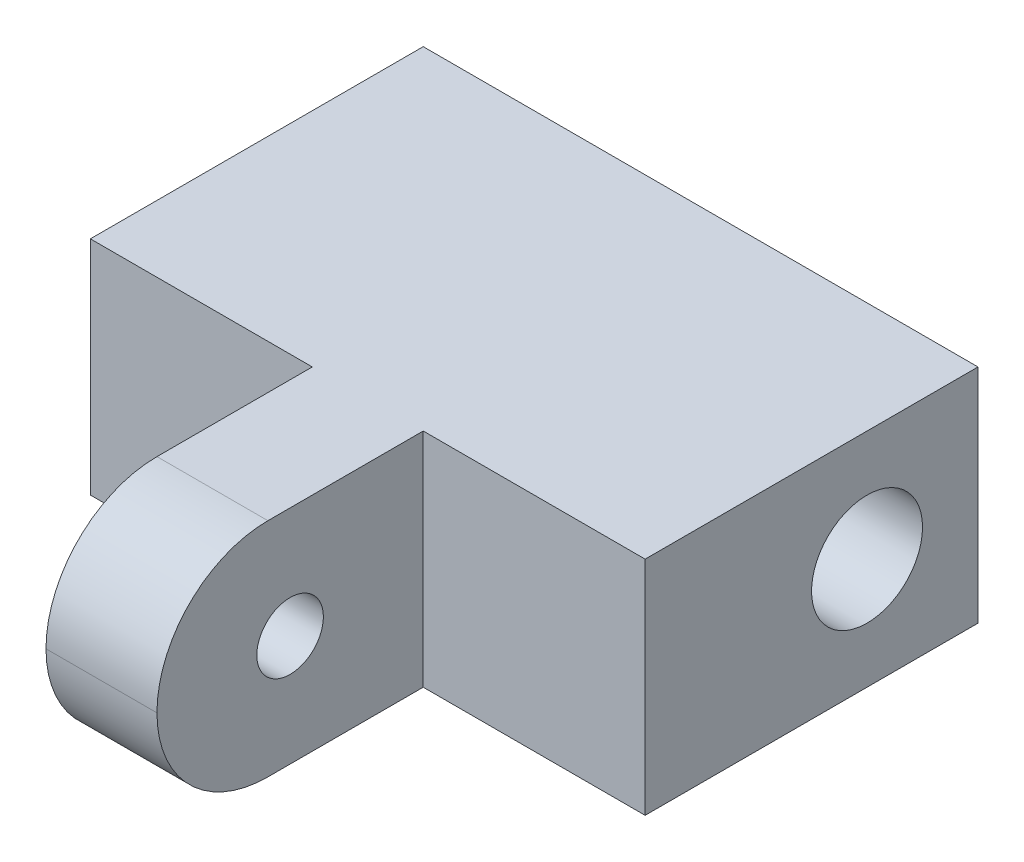
SolidWorks part; units mm, degrees
ref_plane "Front Plane" through (0, 0, 0) normal (0, 0, 1) x (1, 0, 0)
ref_plane "Top Plane" through (0, 0, 0) normal (0, 1, 0) x (1, 0, 0)
ref_plane "Right Plane" through (0, 0, 0) normal (1, 0, 0) x (0, 0, -1)
sketch "Sketch1" plane through (0, 0, 0) normal (0, 1, 0) x (1, 0, 0)
  line L0 (2.5, 0) -> (-2.5, 0)
  line L1 (-2.5, 0) -> (-2.5, 12)
  line L2 (-2.5, 12) -> (-12.5, 12)
  line L3 (-12.5, 12) -> (-12.5, 27)
  line L4 (-12.5, 27) -> (12.5, 27)
  line L5 (12.5, 27) -> (12.5, 12)
  line L6 (12.5, 12) -> (2.5, 12)
  line L7 (2.5, 12) -> (2.5, 0)
  point P4 (0, 0)
  dimension "D1" = 12
  dimension "D2" = 5
  dimension "D3" = 15
  dimension "D4" = 25
extrude "Boss-Extrude1" add sketch "Sketch1" along normal blind 10
sketch "Sketch2" plane through (12.5, 0, 0) normal (1, 0, 0) x (0, 0, -1)
  line L0 (0, 10) -> (0, 0) construction
  line L1 (0, 10) -> (12, 10) construction
  line L2 (27, 10) -> (27, 0) construction
  circle A0 centre (22, 5) radius 2.5
  circle A1 centre (6, 5) radius 1.5
  point P6 (0, 5)
  point P9 (6, 10)
  dimension "D1" = 5
  dimension "D2" = 3
  dimension "D3" = 5
extrude "Cut-Extrude1" cut sketch "Sketch2" against normal through all
fillet "Fillet1" radius 5 2 edges at (0, 10, 0) (0, 0, 0)
